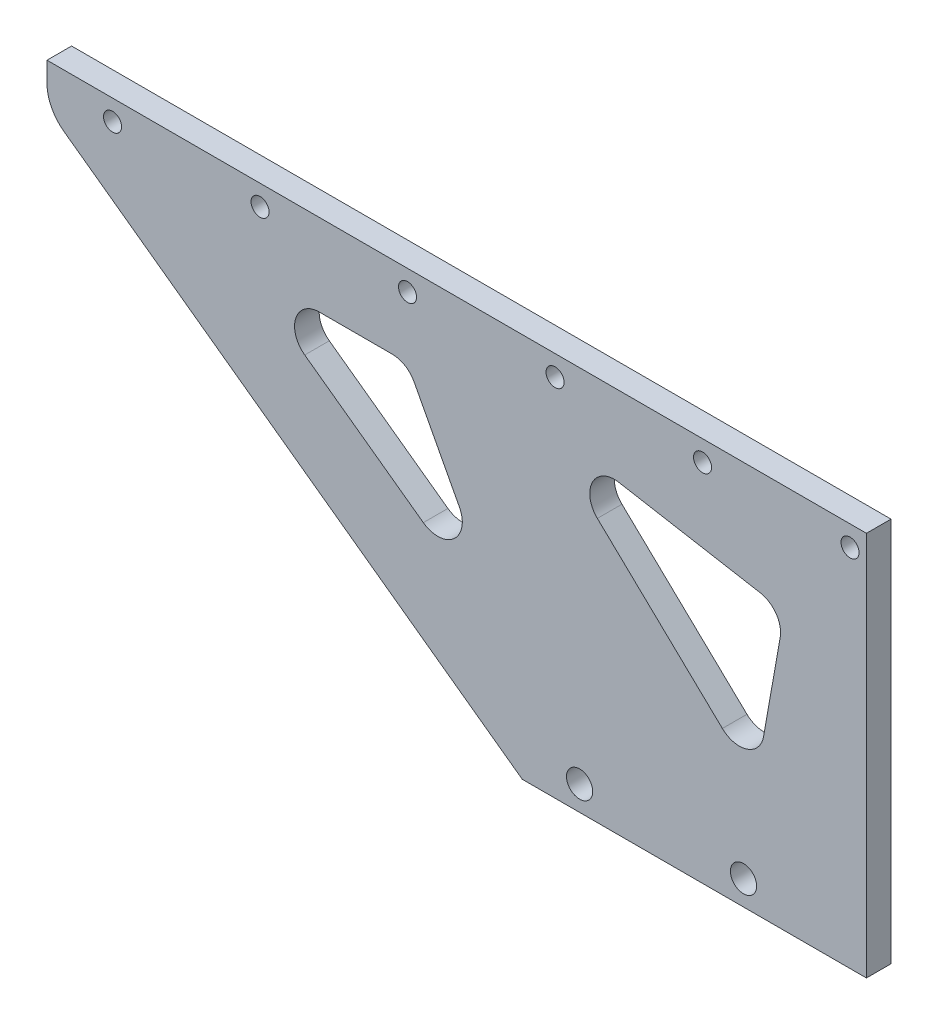
SolidWorks part; units mm, degrees
material "Thornel Mat VMA"
ref_plane "Front" through (0, 0, 0) normal (0, 0, 1) x (1, 0, 0)
ref_plane "Top" through (0, 0, 0) normal (0, 1, 0) x (1, 0, 0)
ref_plane "Right" through (0, 0, 0) normal (1, 0, 0) x (0, 0, -1)
sketch "草图1" plane through (0, 0, 0) normal (0, 0, 1) x (1, 0, 0)
  line L0 (0, 0) -> (0, -47)
  line L1 (0, -47) -> (-42, -47)
  line L2 (-42, -47) -> (-100, -5)
  line L3 (-100, -5) -> (-100, 0)
  line L4 (-100, 0) -> (0, 0)
  dimension "D1" = 47
  dimension "D2" = 100
  dimension "D3" = 42
  dimension "D4" = 5
extrude "凸台-拉伸1" add sketch "草图1" along normal blind 3
sketch "草图2" plane through (0, 0, 3) normal (0, 0, 1) x (1, 0, 0)
  line L0 (0, -47) -> (0, 0) construction
  line L1 (-20, 0) -> (-20, -50000) construction
  line L2 (0, 0) -> (-100, 0) construction
  line L3 (-42, -47) -> (0, -47) construction
  line L4 (-2, -2.5) -> (-100.0424, -2.5) construction
  line L5 (-2, -2.5) -> (-2, -44) construction
  line L6 (-2, -44) -> (-42.7329, -44) construction
  line L7 (-42.7329, -44) -> (-100.0424, -2.5) construction
  line L8 (-100, -5) -> (-42, -47) construction
  circle A0 centre (-38, -35) radius 1.1
  circle A1 centre (-38, -14.5) radius 1.1
  circle A2 centre (-38, -2.5) radius 1.1
  circle A3 centre (-56, -2.5) radius 1.1
  circle A4 centre (-74, -2.5) radius 1.1
  circle A5 centre (-92, -2.5) radius 1.1
  circle A6 centre (-56.5019, -34.0293) radius 1.025
  circle A7 centre (-69.6096, -24.8539) radius 1.025
  circle A8 centre (-82.7173, -15.6785) radius 1.025
  circle A112 centre (-20, -2.5) radius 1.1
  circle A115 centre (-2, -2.5) radius 1.1
  circle A118 centre (-2, -14.5) radius 1.1
  circle A121 centre (-2, -35) radius 1.1
  circle A124 centre (-15, -44) radius 1.6
  circle A127 centre (-35, -44) radius 1.6
  dimension "D3" = 3.2
  dimension "D4" = 3.2
  dimension "D10" = 2.2
  dimension "D11" = 2.2
  dimension "D12" = 2.2
  dimension "D13" = 2.2
  dimension "D18" = 2.05
  dimension "D21" = 16
  dimension "D1" = 20
  dimension "D2" = 15
  dimension "D5" = 3
  dimension "D6" = 12
  dimension "D7" = 12
  dimension "D8" = 2.5
  dimension "D9" = 2
  dimension "D14" = 20.5
  dimension "D15" = 20
  dimension "D16" = 18
  dimension "D17" = 2
  dimension "D19" = 3
  dimension "D20" = 17
extrude "切除-拉伸2" cut sketch "草图2" against normal through all
fillet "圆角1" radius 5 1 edges at (-100, -5, 1.5)
sketch "草图3" plane through (0, 0, 3) normal (0, 0, 1) x (1, 0, 0)
  line L5 (-100, 0) -> (-100, -2.4474)
  line L6 (-97.9325, -6.4971) -> (-42, -47)
  line L7 (-42, -47) -> (0, -47)
  line L8 (0, -47) -> (0, 0)
  line L9 (0, 0) -> (-100, 0)
  line L10 (-100, 0) -> (-100, -2.4474)
  line L11 (-97.9325, -6.4971) -> (-42, -47)
  line L12 (-42, -47) -> (0, -47)
  line L13 (0, -47) -> (0, 0)
  line L14 (0, 0) -> (-100, 0)
  circle A0 centre (-92, -2.5) radius 1.1 construction
  arc A1 (-100, -2.4474) -> (-97.9325, -6.4971) centre (-95, -2.4474) ccw
  arc A2 (-100, -2.4474) -> (-97.9325, -6.4971) centre (-95, -2.4474) ccw
  circle A3 centre (-15, -44) radius 1.6
  circle A4 centre (-15, -44) radius 1.6
  circle A5 centre (-35, -44) radius 1.6
  circle A6 centre (-35, -44) radius 1.6
  circle A7 centre (-2, -2.5) radius 1.1
  circle A8 centre (-2, -2.5) radius 1.1
  circle A9 centre (-20, -2.5) radius 1.1
  circle A10 centre (-20, -2.5) radius 1.1
  circle A11 centre (-38, -2.5) radius 1.1
  circle A12 centre (-38, -2.5) radius 1.1
  circle A13 centre (-56, -2.5) radius 1.1
  circle A14 centre (-56, -2.5) radius 1.1
  circle A15 centre (-74, -2.5) radius 1.1
  circle A16 centre (-74, -2.5) radius 1.1
  circle A17 centre (-92, -2.5) radius 1.1
  dimension "D1" = 0
  dimension "D2" = 0
  dimension "D3" = 0
  dimension "D4" = 0
  dimension "D5" = 0
  dimension "D6" = 0
  dimension "D7" = 0
  dimension "D8" = 0
extrude "凸台-拉伸2" add sketch "草图3" against normal up to surface (3 mm away) up to face at (-13.4, -44, 0)
sketch "草图4" plane through (0, 0, 3) normal (0, 0, 1) x (1, 0, 0)
  line L0 (-76.0452, -10) -> (-43.6475, -33.4604)
  line L1 (-97.9325, -6.4971) -> (-42, -47) construction
  line L2 (-76.0452, -10) -> (-56.0452, -10)
  line L3 (-56.0452, -10) -> (-43.6475, -33.4604)
  line L4 (0, 0) -> (-100, 0) construction
  line L5 (-40, -8) -> (-10, -13.2898)
  line L6 (-10, -13.2898) -> (-13.5265, -33.2898)
  line L7 (-13.5265, -33.2898) -> (-40, -8)
  line L8 (0, -47) -> (0, 0) construction
  dimension "D1" = 40
  dimension "D2" = 10
  dimension "D3" = 20
  dimension "D4" = 10
  dimension "D5" = 20
  dimension "D6" = 30
  dimension "D7" = 10
  dimension "D8" = 8
  dimension "D9" = 10
extrude "切除-拉伸3" cut sketch "草图4" against normal blind 10
fillet "圆角2" radius 3 6 edges at (-10, -13.2898, 1.5) (-13.5265, -33.2898, 1.5) (-56.0452, -10, 1.5) (-43.6475, -33.4604, 1.5) (-76.0452, -10, 1.5) (-40, -8, 1.5)
